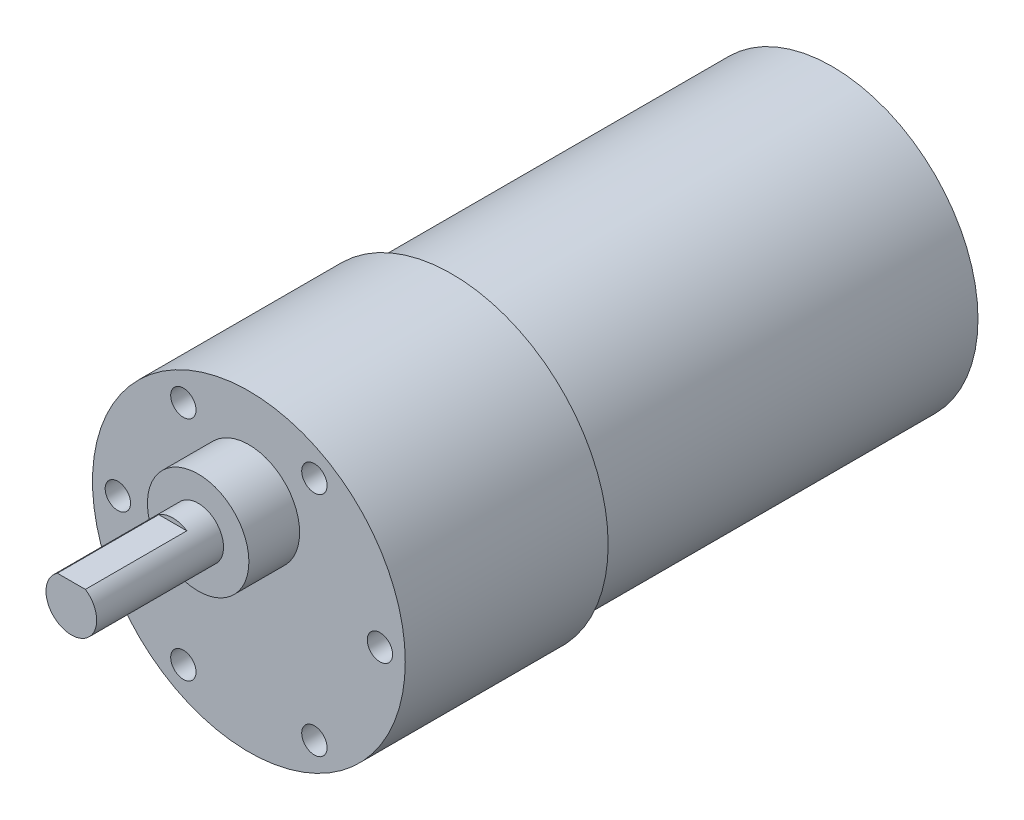
SolidWorks part; units mm, degrees
ref_plane "Front Plane" through (0, 0, 0) normal (0, 0, 1) x (1, 0, 0)
ref_plane "Top Plane" through (0, 0, 0) normal (0, 1, 0) x (1, 0, 0)
ref_plane "Right Plane" through (0, 0, 0) normal (1, 0, 0) x (0, 0, -1)
sketch "Sketch1" plane through (0, 0, 0) normal (0, 0, 1) x (1, 0, 0)
  circle A0 centre (0, 0) radius 18.5
  dimension "D1" = 37
extrude "Boss-Extrude1" add sketch "Sketch1" along normal blind 24
sketch "Sketch2" plane through (0, 0, 0) normal (0, 0, -1) x (-1, 0, 0)
  circle A0 centre (0, 0) radius 17.25
  dimension "D1" = 34.5
extrude "Boss-Extrude2" add sketch "Sketch2" along normal blind 45
sketch "Sketch3" plane through (0, 0, 24) normal (0, 0, 1) x (1, 0, 0)
  line L0 (0, 0) -> (0, 18.5) construction
  circle A0 centre (0, 0) radius 18.5 construction
  circle A1 centre (0, 7) radius 6
  dimension "D2" = 12
  dimension "D1" = 7
extrude "Boss-Extrude3" add sketch "Sketch3" along normal blind 6
sketch "Sketch4" plane through (0, 0, 30) normal (0, 0, 1) x (1, 0, 0)
  circle A0 centre (0, 7) radius 3
  circle A1 centre (0, 7) radius 6 construction
  dimension "D1" = 6
extrude "Boss-Extrude4" add sketch "Sketch4" along normal blind 15
sketch "Sketch5" plane through (0, 0, 45) normal (0, 0, 1) x (1, 0, 0)
  line L0 (-1.6583, 9.5) -> (1.6583, 9.5)
  line L1 (0, 9.5) -> (0, 4)
  circle A0 centre (0, 7) radius 3
  circle A1 centre (0, 7) radius 3 construction
  circle M1 centre (0, 7) radius 3
  dimension "D1" = 5.5
extrude "Cut-Extrude1" cut sketch "Sketch5" against normal blind 12 contours L0 M1 region at (0, 9.7015, 45)
sketch "Sketch6" plane through (0, 0, 24) normal (0, 0, 1) x (1, 0, 0)
  line L0 (0, 18.5) -> (0, 0) construction
  line L1 (0, 0) -> (9.25, 16.0215) construction
  circle A0 centre (7.75, 13.4234) radius 1.5
  circle A3 centre (0, 0) radius 18.5 construction
  circle A4 centre (0, 0) radius 15.5 construction
  circle A5 centre (15.5, 0) radius 1.5
  circle A6 centre (7.75, -13.4234) radius 1.5
  circle A7 centre (-7.75, -13.4234) radius 1.5
  circle A8 centre (-15.5, 0) radius 1.5
  circle A9 centre (-7.75, 13.4234) radius 1.5
  point P21 (0, 0)
  dimension "D2" = 31
  dimension "D4" = 3
  dimension "D1" = 30
  dimension "D3" = 6
extrude "Cut-Extrude2" cut sketch "Sketch6" against normal blind 3
